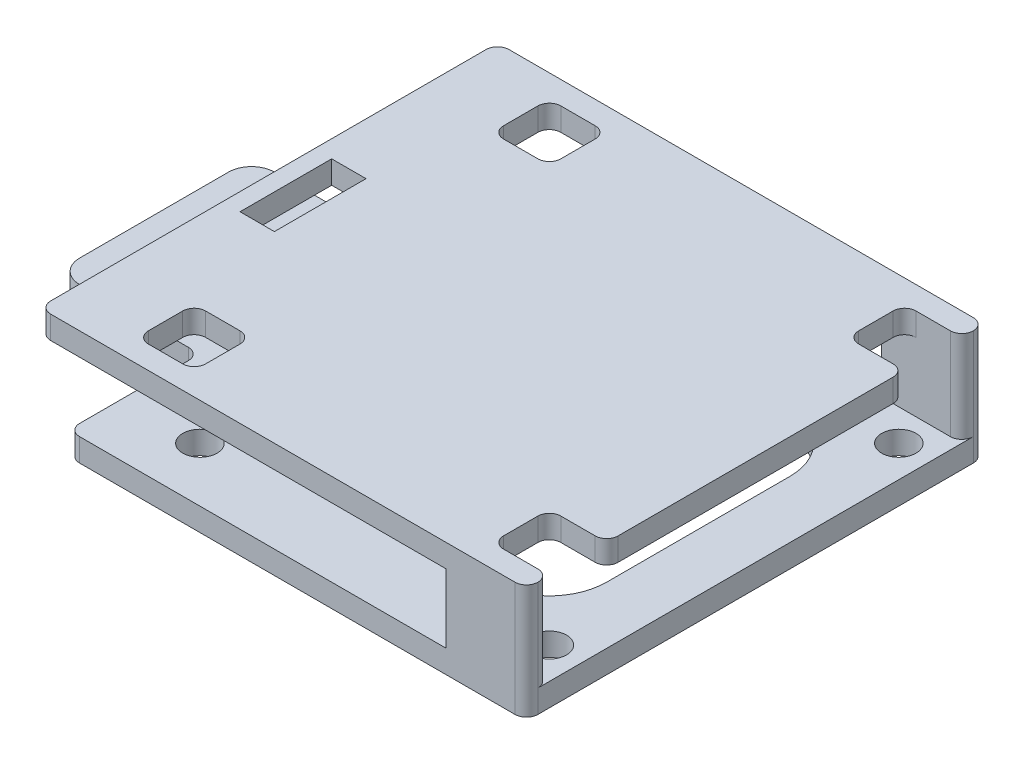
SolidWorks part; units mm, degrees
ref_plane "Alzado" through (0, 0, 0) normal (0, 0, 1) x (1, 0, 0)
ref_plane "Planta" through (0, 0, 0) normal (0, 1, 0) x (1, 0, 0)
ref_plane "Vista lateral" through (0, 0, 0) normal (1, 0, 0) x (0, 0, -1)
sketch "Croquis1" plane through (0, 0, 0) normal (0, 1, 0) x (1, 0, 0)
  line L0 (-13, -13) -> (-13, 13)
  line L1 (-18, -18) -> (18, -18)
  line L2 (-18, -18) -> (-18, 18)
  line L3 (-18, 18) -> (18, 18)
  line L4 (18, -18) -> (18, 18)
  line L5 (-18, -18) -> (18, 18) construction
  line L6 (-18, 18) -> (18, -18) construction
  line L7 (-1.5, -8.5) -> (-34.5, -8.5)
  line L8 (-1.5, -8.5) -> (-1.5, 8.5)
  line L9 (-1.5, 8.5) -> (-34.5, 8.5)
  line L10 (-34.5, -8.5) -> (-34.5, 8.5)
  line L11 (-1.5, -8.5) -> (-34.5, 8.5) construction
  line L12 (-1.5, 8.5) -> (-34.5, -8.5) construction
  line L13 (-13, 13) -> (13, 13)
  line L14 (13, -13) -> (13, 13)
  line L15 (-13, -13) -> (13, -13)
  line L16 (0, 0) -> (26.5357, 0) construction
  line L17 (0, 0) -> (0, 23.2513) construction
  circle A0 centre (-15.25, 15.25) radius 1.5
  circle A1 centre (-15.25, -15.25) radius 1.5
  circle A2 centre (15.25, -15.25) radius 1.5
  circle A3 centre (15.25, 15.25) radius 1.5
  point P0 (0, 0)
  point P6 (-18, 0)
  dimension "D5" = 3
  dimension "D1" = 36
  dimension "D2" = 52.5
  dimension "D3" = 17
  dimension "D6" = 15.25
  dimension "D4" = 5
extrude "Saliente-Extruir1" add sketch "Croquis1" along normal blind 2 contours L10 L7 L2 L9 | L15 L0 L7 L2 L1 L4 L3 L9 L13 L14 A1 A0 A2 A3 | L0 L9 L2 L7 region at (0, 0, 13.5091) region at (-15.5, 0, 0) region at (-26.25, 0, 0)
sketch "Croquis2" plane through (0, 2, 0) normal (0, 1, 0) x (1, 0, 0)
  line L0 (18, 20) -> (18, -20)
  line L1 (18, -20) -> (-22, -20)
  line L2 (-22, -20) -> (-22, 20)
  line L3 (-22, 20) -> (18, 20)
  line L9 (-34.5, -8.5) -> (-1.5, -8.5)
  line L10 (-34.5, 8.5) -> (-34.5, -8.5)
  line L11 (-1.5, 8.5) -> (-34.5, 8.5)
  line L12 (-1.5, -8.5) -> (-1.5, 8.5)
  line L13 (-34.5, -8.5) -> (-1.5, -8.5)
  line L14 (-34.5, 8.5) -> (-34.5, -8.5)
  line L15 (-1.5, 8.5) -> (-34.5, 8.5)
  line L16 (-1.5, -8.5) -> (-1.5, 8.5)
  line L17 (-18, -18) -> (18, -18)
  line L18 (18, -18) -> (18, 18)
  line L19 (18, 18) -> (-18, 18)
  line L20 (-18, 18) -> (-18, -18)
  line L21 (-18, -18) -> (18, -18)
  line L22 (18, -18) -> (18, 18)
  line L23 (18, 18) -> (-18, 18)
  line L24 (-18, 18) -> (-18, -18)
  line L25 (-13, 13) -> (-13, -13)
  line L26 (13, 13) -> (-13, 13)
  line L27 (13, -13) -> (13, 13)
  line L28 (-13, -13) -> (13, -13)
  line L29 (-13, 13) -> (-13, -13)
  line L30 (13, 13) -> (-13, 13)
  line L31 (13, -13) -> (13, 13)
  line L32 (-13, -13) -> (13, -13)
  circle A1 centre (15.25, 15.25) radius 1.5
  circle A2 centre (15.25, 15.25) radius 1.5
  circle A3 centre (15.25, -15.25) radius 1.5
  circle A4 centre (15.25, -15.25) radius 1.5
  circle A5 centre (-15.25, -15.25) radius 1.5
  circle A6 centre (-15.25, -15.25) radius 1.5
  circle A7 centre (-15.25, 15.25) radius 1.5
  circle A8 centre (-15.25, 15.25) radius 1.5
  line M5 (-18, 18) -> (-18, 8.5)
  line M6 (-18, 8.5) -> (-34.5, 8.5)
  line M8 (-34.5, -8.5) -> (-18, -8.5)
  line M9 (-18, -8.5) -> (-18, -18)
  line M10 (-18, -18) -> (18, -18)
  line M12 (18, 18) -> (-18, 18)
  dimension "D1" = 40
  dimension "D2" = 20
  dimension "D3" = 40
  dimension "D4" = 0
  dimension "D5" = 0
  dimension "D6" = 0
  dimension "D7" = 0
  dimension "D8" = 0
  dimension "D9" = 0
  dimension "D10" = 0
extrude "Saliente-Extruir2" add sketch "Croquis2" against normal up to surface (2 mm away) contours L3 L2 L0 M6 M5 M12 | L2 L1 L0 M10 M9 M8 region at (17.5838, 2, -19) region at (17.5838, 2, 19) up to face at (-13.125, 0, 0)
sketch "Croquis4" plane through (0, 2, 0) normal (0, 1, 0) x (1, 0, 0)
  line L0 (0, 0) -> (36.8901, 0) construction
  line L1 (18, -20) -> (11, -20)
  line L2 (18, -20) -> (18, -18)
  line L3 (18, -18) -> (11, -18)
  line L4 (11, -20) -> (11, -18)
  line L5 (18, 18) -> (11, 18)
  line L10 (11, 20) -> (11, 18)
  line L11 (18, 20) -> (11, 20)
  line L12 (18, 20) -> (18, 18)
  dimension "D1" = 7
  dimension "D2" = 2
extrude "Saliente-Extruir3" add sketch "Croquis4" along normal blind 6
sketch "Croquis7" plane through (0, 8, 0) normal (0, 1, 0) x (1, 0, 0)
  line L1 (18, -20) -> (-24.5225, -20)
  line L2 (18, -20) -> (18, 20)
  line L3 (18, 20) -> (-24.5225, 20)
  line L4 (-24.5225, -20) -> (-24.5225, 20)
extrude "Saliente-Extruir5" add sketch "Croquis7" along normal blind 2
sketch "Croquis8" plane through (0, 10, 0) normal (0, 1, 0) x (1, 0, 0)
  line L1 (18, -18) -> (13, -18)
  line L2 (18, -18) -> (18, -13)
  line L3 (18, -13) -> (13, -13)
  line L4 (13, -18) -> (13, -13)
  line L5 (13, 13) -> (18, 13)
  line L6 (13, 13) -> (13, 18)
  line L7 (13, 18) -> (18, 18)
  line L8 (18, 13) -> (18, 18)
  line L9 (-13, 13) -> (-18, 13)
  line L10 (-13, 13) -> (-13, 18)
  line L11 (-13, 18) -> (-18, 18)
  line L12 (-18, 13) -> (-18, 18)
  line L13 (-13, -13) -> (-18, -13)
  line L14 (-13, -13) -> (-13, -18)
  line L15 (-13, -18) -> (-18, -18)
  line L16 (-18, -13) -> (-18, -18)
extrude "Cortar-Extruir1" cut sketch "Croquis8" against normal up to next
fillet "Redondeo1" radius 5 4 edges at (13, 1, -13) (13, 1, 13) (-13, 1, 13) (-13, 1, -13)
fillet "Redondeo2" radius 2 2 edges at (-34.5, 1, 8.5) (-34.5, 1, -8.5)
sketch "Croquis10" plane through (0, 10, 0) normal (0, 1, 0) x (1, 0, 0)
  line L0 (18, -13) -> (18, 13) construction
  line L1 (-19.5, 4.5) -> (-23.5, 4.5)
  line L2 (-19.5, 4.5) -> (-19.5, -4.5)
  line L3 (-19.5, -4.5) -> (-23.5, -4.5)
  line L4 (-23.5, 4.5) -> (-23.5, -4.5)
  point P9 (-1.2271, 0.8136)
  dimension "D1" = 37.5
  dimension "D2" = 4
  dimension "D3" = 4.5
  dimension "D4" = 4.5
sketch "Croquis12" plane through (0, 10, 0) normal (0, 1, 0) x (1, 0, 0)
  line L0 (-20, 4) -> (-23, 4)
  line L1 (-23, 4) -> (-23, -4)
  line L2 (-23, -4) -> (-20, -4)
  line L3 (-20, -4) -> (-20, 4)
  line L4 (-19.5, 4.5) -> (-23.5, 4.5)
  line L5 (-23.5, 4.5) -> (-23.5, -4.5)
  line L6 (-23.5, -4.5) -> (-19.5, -4.5)
  line L7 (-19.5, -4.5) -> (-19.5, 4.5)
  line L8 (-19.5, 4.5) -> (-23.5, 4.5)
  line L9 (-23.5, 4.5) -> (-23.5, -4.5)
  line L10 (-23.5, -4.5) -> (-19.5, -4.5)
  line L11 (-19.5, -4.5) -> (-19.5, 4.5)
  line L12 (18, 13) -> (13, 13)
  line L13 (13, 13) -> (13, 18)
  line L14 (13, 18) -> (18, 18)
  line L15 (18, 18) -> (18, 20)
  line L16 (18, 20) -> (-24.5225, 20)
  line L17 (-24.5225, 20) -> (-24.5225, -20)
  line L18 (-24.5225, -20) -> (18, -20)
  line L19 (18, -20) -> (18, -18)
  line L20 (18, -18) -> (13, -18)
  line L21 (13, -18) -> (13, -13)
  line L22 (13, -13) -> (18, -13)
  line L23 (18, -13) -> (18, 13)
  line L24 (18, 13) -> (13, 13)
  line L25 (13, 13) -> (13, 18)
  line L26 (13, 18) -> (18, 18)
  line L27 (18, 18) -> (18, 20)
  line L28 (18, 20) -> (-24.5225, 20)
  line L29 (-24.5225, 20) -> (-24.5225, -20)
  line L30 (-24.5225, -20) -> (18, -20)
  line L31 (18, -20) -> (18, -18)
  line L32 (18, -18) -> (13, -18)
  line L33 (13, -18) -> (13, -13)
  line L34 (13, -13) -> (18, -13)
  line L35 (18, -13) -> (18, 13)
  dimension "D1" = 0
  dimension "D2" = 0
  dimension "D3" = 0.5
extrude "Cortar-Extruir3" cut sketch "Croquis12" against normal up to next contours L2 L3 L0 L1 region at (-21.5, 10, 0)
fillet "Redondeo3" radius 1 24 edges at (-22, 1, -8.5) (-22, 1, 8.5) (-13, 9, 18) (-18, 9, 18) (-18, 9, 13) (-13, 9, 13) (-13, 9, -13) (-18, 9, -18) (-18, 9, -13) (-13, 9, -18) (-24.5225, 9, -20) (-22, 1, -20) (18, 5, -20) (18, 6, -18) (18, 9, -13) (13, 9, -18) (13, 9, -13) (13, 9, 18) (13, 9, 13) (18, 9, 13) (18, 6, 18) (18, 5, 20) (-22, 1, 20) (-24.5225, 9, 20)
